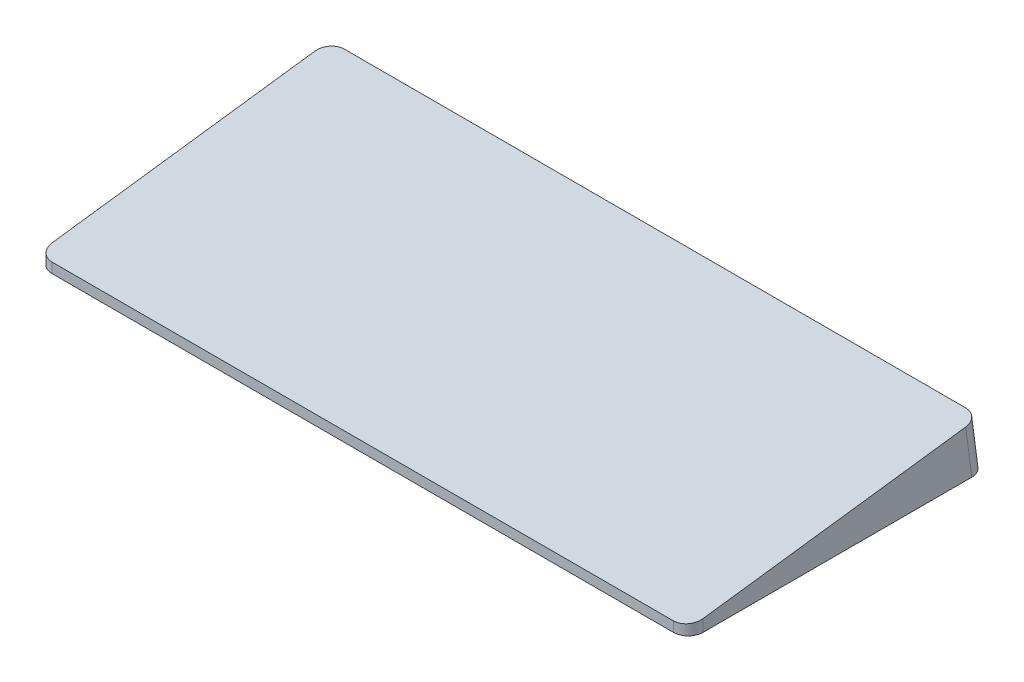
SolidWorks part; units mm, degrees
ref_plane "Front Plane" through (0, 0, 0) normal (0, 0, 1) x (1, 0, 0)
ref_plane "Top Plane" through (0, 0, 0) normal (0, 1, 0) x (1, 0, 0)
ref_plane "Right Plane" through (0, 0, 0) normal (1, 0, 0) x (0, 0, -1)
sketch "Sketch1" plane through (0, 0, 0) normal (0, 1, 0) x (1, 0, 0)
  line L1 (-165, 75.665) -> (165, 75.665)
  line L2 (-165, 75.665) -> (-165, -75.665)
  line L3 (-165, -75.665) -> (165, -75.665)
  line L4 (165, 75.665) -> (165, -75.665)
  line L5 (-165, 75.665) -> (165, -75.665) construction
  line L6 (-165, -75.665) -> (165, 75.665) construction
  point P0 (0, 0)
  dimension "D1" = 330
  dimension "D2" = 151.33
extrude "Boss-Extrude1" add sketch "Sketch1" along normal blind 25
sketch "Sketch2" plane through (0, 0, 0) normal (1, 0, 0) x (0, 0, -1)
  line L0 (-75.665, 5.077) -> (75.665, 25)
  line L1 (-75.665, 25) -> (-75.665, 0) construction
  line L2 (75.665, 25) -> (-75.665, 25)
  line L3 (-75.665, 25) -> (75.665, 25) construction
  line L4 (-75.665, 25) -> (-75.665, 5.077)
  line L5 (75.665, 0) -> (72.4298, 24.5741)
  line L6 (75.665, 25) -> (75.665, 0) construction
  line L7 (75.665, 25) -> (75.665, 0)
  dimension "D1" = 7.5
extrude "Cut-Extrude1" cut sketch "Sketch2" against normal through all both and the other way through all contours L2 L4 L0 | L7 L0 L5 region at (0, 18.359, 25.2217) region at (0, 16.5247, -74.5866)
fillet "Fillet1" radius 7.5 4 edges at (-165, 2.5385, 75.665) (165, 2.5385, 75.665) (-165, 12.287, -74.0474) (165, 12.287, -74.0474)
sketch "Sketch3" plane through (0, 0, 0) normal (0, -1, 0) x (1, 0, 0)
  line L1 (-125, 30) -> (125, 30)
  line L2 (-125, 30) -> (-125, -70)
  line L3 (-125, -70) -> (125, -70)
  line L4 (125, 30) -> (125, -70)
  point P5 (0, 30)
  dimension "D1" = 250
  dimension "D2" = 100
  dimension "D3" = 30
extrude "Cut-Extrude2" cut sketch "Sketch3" against normal blind 3
sketch "Sketch4" plane through (0, 0, 0) normal (0, 1, 0) x (1, 0, 0)
  line L1 (-160.1297, 68.0505) -> (160.1297, 68.0505)
  line L2 (-160.1297, 68.0505) -> (-160.1297, -68.0505)
  line L3 (-160.1297, -68.0505) -> (160.1297, -68.0505)
  line L4 (160.1297, 68.0505) -> (160.1297, -68.0505)
  line L5 (-160.1297, 68.0505) -> (160.1297, -68.0505) construction
  line L6 (-160.1297, -68.0505) -> (160.1297, 68.0505) construction
  point P0 (0, 0)
extrude "Cut-Extrude3" [suppressed] cut sketch "Sketch4" against normal blind 10 from surface starting at face at (0, 14.8272, 1.6049)
